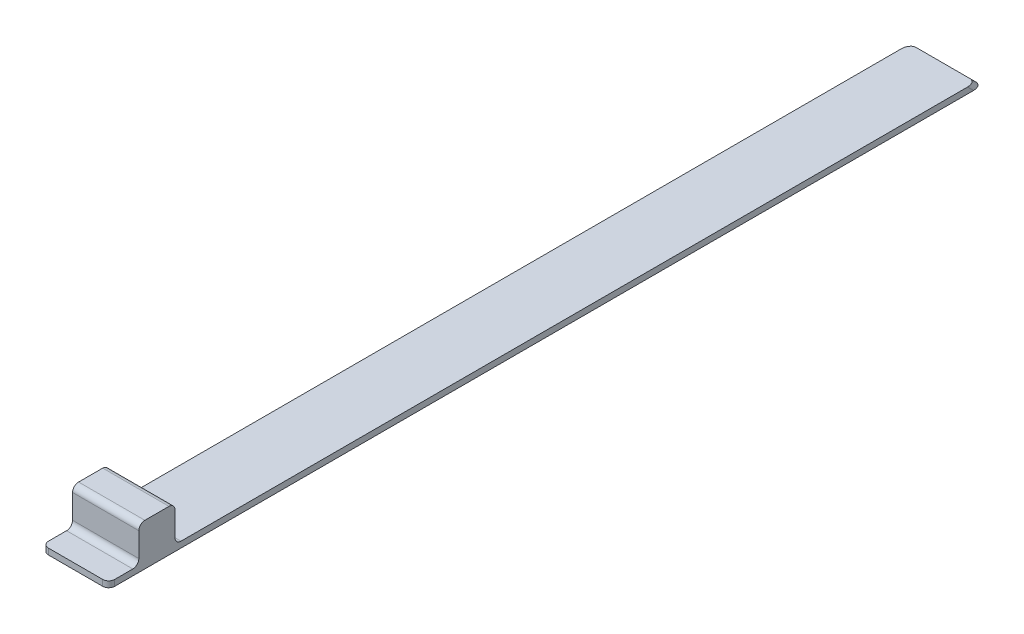
SolidWorks part; units mm, degrees
ref_plane "Front Plane" through (0, 0, 0) normal (0, 0, 1) x (1, 0, 0)
ref_plane "Top Plane" through (0, 0, 0) normal (0, 1, 0) x (1, 0, 0)
ref_plane "Right Plane" through (0, 0, 0) normal (1, 0, 0) x (0, 0, -1)
sketch "Szkic1" plane through (0, 0, 0) normal (0, 1, 0) x (1, 0, 0)
  line L0 (-5.5, -72.5) -> (5.5, 72.5) construction
  line L1 (-5.5, 72.5) -> (5.5, 72.5)
  line L2 (-5.5, 72.5) -> (-5.5, -72.5)
  line L3 (-5.5, -72.5) -> (5.5, -72.5)
  line L4 (5.5, 72.5) -> (5.5, -72.5)
  dimension "D1" = 11
  dimension "D2" = 145
extrude "Dodanie-wyciągnięcie1" add sketch "Szkic1" along normal blind 1
chamfer "Sfazowanie1" distance 1 angle 45 1 edges at (0, 1, -72.5)
sketch "Szkic2" plane through (0, 1, 0) normal (0, 1, 0) x (1, 0, 0)
  line L0 (-5.5, 71.5) -> (-5.5, -72.5) construction
  line L1 (-5.5, -67.5) -> (5.5, -67.5)
  line L2 (-5.5, -67.5) -> (-5.5, -61.5)
  line L3 (-5.5, -61.5) -> (5.5, -61.5)
  line L4 (5.5, -67.5) -> (5.5, -61.5)
  line L5 (5.5, -72.5) -> (5.5, 71.5) construction
  line L6 (-5.5, -72.5) -> (5.5, -72.5) construction
  dimension "D1" = 6
  dimension "D2" = 5
extrude "Dodanie-wyciągnięcie2" add sketch "Szkic2" along normal blind 6
fillet "Zaokrąglenie1" radius 1 8 edges at (0, 1, 61.5) (0, 7, 61.5) (0, 7, 67.5) (0, 1, 67.5) (-5.5, 0.5, 72.5) (5.5, 0.5, 72.5) (5.5, 0.5, -72) (-5.5, 0.5, -72)
